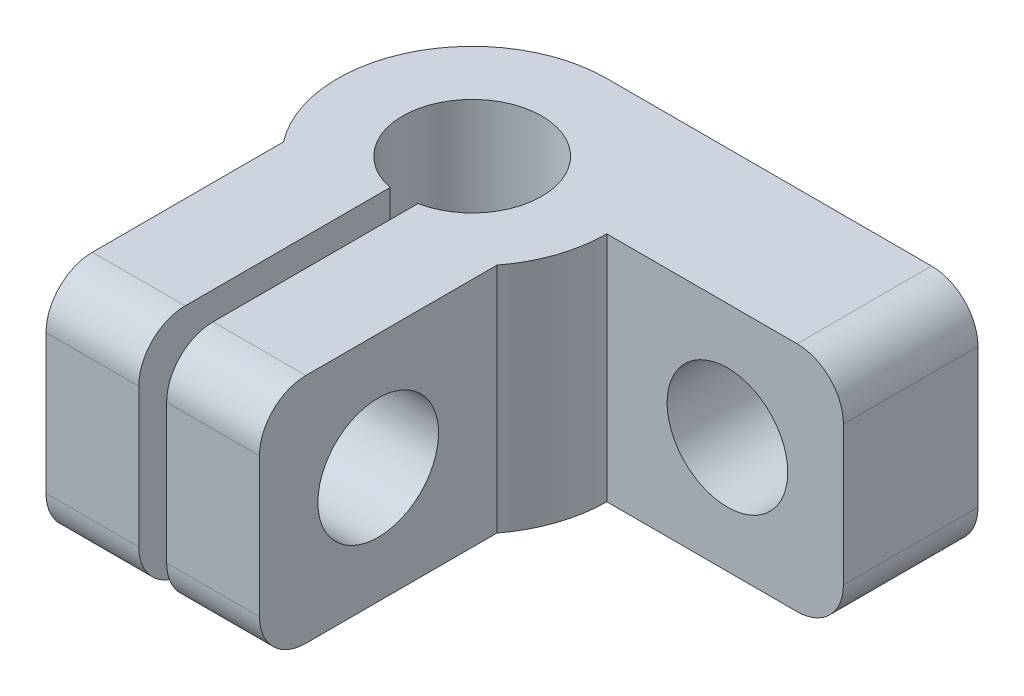
SolidWorks part; units mm, degrees
ref_plane "Front Plane" through (0, 0, 0) normal (0, 0, 1) x (1, 0, 0)
ref_plane "Top Plane" through (0, 0, 0) normal (0, 1, 0) x (1, 0, 0)
ref_plane "Right Plane" through (0, 0, 0) normal (1, 0, 0) x (0, 0, -1)
sketch "Sketch1" plane through (0, 0, 0) normal (0, 1, 0) x (1, 0, 0)
  line L0 (0, 2.9) -> (8, 2.9)
  line L1 (8, 2.9) -> (8, 0)
  line L2 (8, 0) -> (2.9, 0)
  line L3 (0, 0) -> (0, -2.9) construction
  line L4 (-0.3, -2.8844) -> (-0.3, -1.4697)
  line L5 (0.3, -2.8844) -> (0.3, -1.4697)
  line L6 (-0.3, -2.8844) -> (-0.3, -6.8844)
  line L7 (-0.3, -6.8844) -> (-2.3, -6.8844)
  line L8 (-2.3, -6.8844) -> (-2.3, -1.7664)
  line L9 (0.3, -2.8844) -> (0.3, -6.8844)
  line L10 (0.3, -6.8844) -> (2.3, -6.8844)
  line L11 (2.3, -6.8844) -> (2.3, -1.7664)
  arc A0 (0.3, -1.4697) -> (-0.3, -1.4697) centre (0, 0) ccw
  arc A1 (0, 2.9) -> (-2.3, -1.7664) centre (0, 0) ccw
  arc A2 (-0.3, -2.8844) -> (0.3, -2.8844) centre (0, 0) ccw
  arc A3 (2.3, -1.7664) -> (2.9, 0) centre (0, 0) ccw
  dimension "D1" = 3
  dimension "D2" = 5.8
  dimension "D7" = 4
  dimension "D3" = 0.3
  dimension "D4" = 0.3
  dimension "D5" = 2
  dimension "D6" = 2
  dimension "D8" = 4
  dimension "D9" = 8
  dimension "D10" = 2.9
extrude "Boss-Extrude1" add sketch "Sketch1" along normal blind 5 contours L11 A3 L2 L1 L0 A1 L8 L7 L6 L4 A0 L5 L9 L10 region at (1.6093, 0, 1.0389)
sketch "Sketch2" plane through (-2.3, 0, 0) normal (-1, 0, 0) x (0, 0, 1)
  line L0 (1.7664, 2.5) -> (6.8844, 2.5) construction
  line L1 (1.7664, 5) -> (1.7664, 0) construction
  line L2 (6.8844, 5) -> (6.8844, 0) construction
  circle A0 centre (4.3254, 2.5) radius 1.3
  dimension "D1" = 2.6
extrude "Cut-Extrude1" cut sketch "Sketch2" against normal through all
sketch "Sketch3" plane through (0, 0, -2.9) normal (0, 0, -1) x (-1, 0, 0)
  line L0 (-8, 2.5) -> (0, 2.5) construction
  line L1 (-8, 5) -> (-8, 0) construction
  line L2 (0, 5) -> (0, 0) construction
  circle A0 centre (-5.5, 2.5) radius 1.3
  dimension "D1" = 2.6
  dimension "D2" = 2.5
extrude "Cut-Extrude2" cut sketch "Sketch3" against normal through all
fillet "Fillet1" radius 1 4 edges at (-1.3, 5, 6.8844) (-1.3, 0, 6.8844) (1.3, 0, 6.8844) (1.3, 5, 6.8844)
fillet "Fillet2" radius 1 2 edges at (8, 0, -1.45) (8, 5, -1.45)
